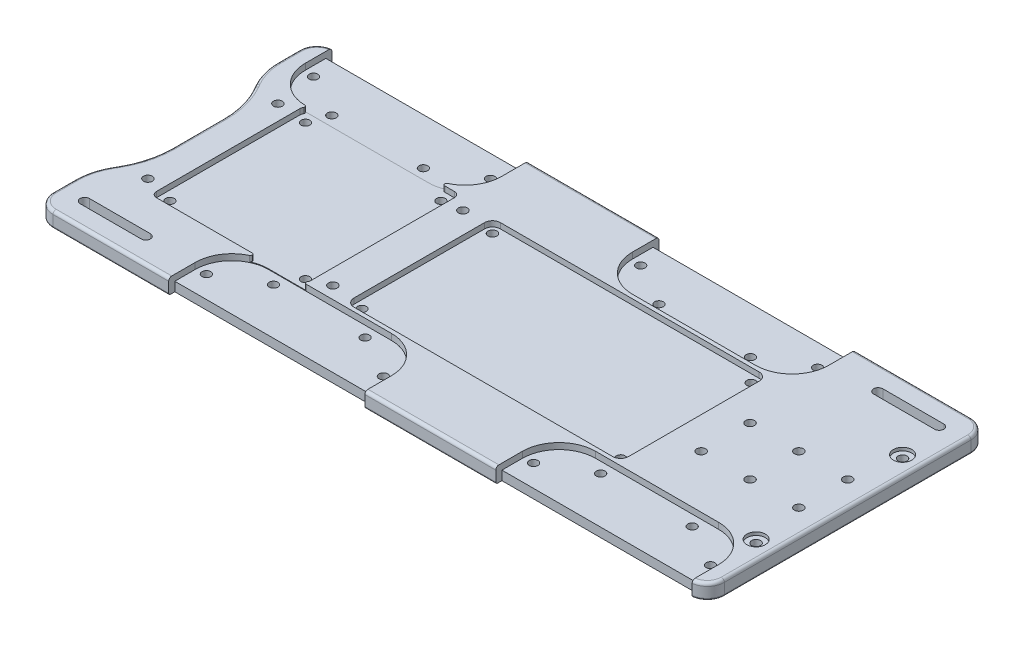
SolidWorks part; units mm, degrees
ref_plane "前视基准面" through (0, 0, 0) normal (0, 0, 1) x (1, 0, 0)
ref_plane "上视基准面" through (0, 0, 0) normal (0, 1, 0) x (1, 0, 0)
ref_plane "右视基准面" through (0, 0, 0) normal (1, 0, 0) x (0, 0, -1)
sketch "草图1" plane through (0, 0, 0) normal (0, 1, 0) x (1, 0, 0)
  line L1 (-105, -46) -> (105, -46)
  line L2 (-105, -46) -> (-105, 46)
  line L3 (-105, 46) -> (105, 46)
  line L4 (105, -46) -> (105, 46)
  line L5 (-105, -46) -> (105, 46) construction
  line L6 (-105, 46) -> (105, -46) construction
  point P0 (0, 0)
  dimension "D1" = 92
  dimension "D2" = 210
extrude "凸台-拉伸1" add sketch "草图1" along normal blind 5
sketch "草图7" plane through (0, 0, 0) normal (0, -1, 0) x (1, 0, 0)
  circle A0 centre (-101.85, -36.8) radius 1.425
  circle A1 centre (-87.85, -28.8) radius 1.425
  circle A2 centre (-57.85, -28.8) radius 1.425
  circle A3 centre (-43.85, -36.8) radius 1.425
  circle A4 centre (5.35, -36.8) radius 1.425
  circle A5 centre (19.35, -28.8) radius 1.425
  circle A6 centre (49.35, -28.8) radius 1.425
  circle A7 centre (63.35, -36.8) radius 1.425
  circle A8 centre (101.85, 36.8) radius 1.425
  circle A9 centre (87.85, 28.8) radius 1.425
  circle A10 centre (57.85, 28.8) radius 1.425
  circle A11 centre (43.85, 36.8) radius 1.425
  circle A12 centre (-5.35, 36.8) radius 1.425
  circle A13 centre (-19.35, 28.8) radius 1.425
  circle A14 centre (-49.35, 28.8) radius 1.425
  circle A15 centre (-63.35, 36.8) radius 1.425
  dimension "D1" = 2.85
  dimension "D2" = 2.85
  dimension "D3" = 2.85
  dimension "D4" = 2.85
  dimension "D5" = 2.85
  dimension "D6" = 2.85
  dimension "D7" = 2.85
  dimension "D8" = 2.85
  dimension "D9" = 2.85
  dimension "D10" = 2.85
  dimension "D11" = 2.85
  dimension "D12" = 2.85
  dimension "D13" = 2.85
  dimension "D14" = 2.85
  dimension "D15" = 2.85
  dimension "D16" = 2.85
extrude "切除-拉伸2" cut sketch "草图7" against normal blind 10
sketch "草图8" plane through (0, 5, 0) normal (0, 1, 0) x (1, 0, 0)
sketch "草图9" plane through (-105, 0, 0) normal (-1, 0, 0) x (0, 0, 1)
  line L1 (-46, 5) -> (46, 5)
  line L2 (-46, 5) -> (-46, 0)
  line L3 (-46, 0) -> (46, 0)
  line L12 (46, 5) -> (46, 0)
extrude "凸台-拉伸2" add sketch "草图9" along normal blind 5
sketch "草图10" plane through (105, 0, 0) normal (1, 0, 0) x (0, 0, -1)
  line L1 (-46, 5) -> (46, 5)
  line L2 (-46, 5) -> (-46, 0)
  line L3 (-46, 0) -> (46, 0)
  line L4 (46, 5) -> (46, 0)
extrude "凸台-拉伸3" add sketch "草图10" along normal blind 5
sketch "草图11" plane through (0, 5, 0) normal (0, 1, 0) x (1, 0, 0)
  line L0 (-110, 0) -> (-110, 28)
  line L2 (-110, 28) -> (-103, 15.8756)
  line L3 (-103, 15.8756) -> (-103, -15.8756)
  line L4 (-103, -15.8756) -> (-110, -28)
  line L5 (-110, -28) -> (-110, 0)
  dimension "D1" = 28
  dimension "D2" = 28
  dimension "D3" = 30
  dimension "D4" = 30
  dimension "D5" = 7
extrude "切除-拉伸4" cut sketch "草图11" against normal blind 5
fillet "圆角1" radius 20 2 edges at (-110, 2.5, 28) (-110, 2.5, -28)
fillet "圆角2" radius 28 2 edges at (-103, 2.5, 15.8756) (-103, 2.5, -15.8756)
fillet "圆角3" radius 5.6 4 edges at (110, 2.5, -46) (-110, 2.5, 46) (110, 2.5, 46) (-110, 2.5, -46)
sketch "草图13" plane through (0, 5, 0) normal (0, 1, 0) x (1, 0, 0)
  line L0 (-103, 0) -> (110, 0) construction
  line L1 (-103, -8.3731) -> (-103, 8.3731) construction
  line L4 (-93, 25.3) -> (-42.4, 25.3)
  line L5 (-93, 25.3) -> (-93, -25.3)
  line L6 (-93, -25.3) -> (-42.4, -25.3)
  line L7 (-42.4, 25.3) -> (-42.4, -25.3)
  line L8 (-93, 25.3) -> (-42.4, -25.3) construction
  line L9 (-93, -25.3) -> (-42.4, 25.3) construction
  point P6 (-67.7, 0)
  dimension "D1" = 50.6
  dimension "D2" = 50.6
  dimension "D3" = 10
extrude "切除-拉伸5" cut sketch "草图13" against normal blind 1.8
fillet "圆角4" radius 1.8 4 edges at (-42.4, 4.1, 25.3) (-93, 4.1, 25.3) (-42.4, 4.1, -25.3) (-93, 4.1, -25.3)
sketch "草图14" plane through (0, 3.2, 0) normal (0, 1, 0) x (1, 0, 0)
  line L0 (-44.2, 25.3) -> (-91.2, 25.3) construction
  line L1 (-93, 23.5) -> (-93, -23.5) construction
  line L2 (-93, 0) -> (-42.4, 0) construction
  line L3 (-93, 23.5) -> (-93, -23.5) construction
  line L4 (-42.4, -23.5) -> (-42.4, 23.5) construction
  line L6 (-67.7, 25.3) -> (-67.7, -25.3) construction
  line L7 (-91.2, -25.3) -> (-44.2, -25.3) construction
  circle A0 centre (-89.9, 22.2) radius 1.425
  circle A1 centre (-45.5, 22.2) radius 1.425
  circle A2 centre (-45.5, -22.2) radius 1.425
  circle A3 centre (-89.9, -22.2) radius 1.425
  dimension "D3" = 2.85
  dimension "D1" = 3.1
  dimension "D2" = 3.1
extrude "切除-拉伸6" cut sketch "草图14" against normal blind 3
sketch "草图15" plane through (0, 5, 0) normal (0, 1, 0) x (1, 0, 0)
  line L0 (-103, 0) -> (110, 0) construction
  line L1 (-103, -8.3731) -> (-103, 8.3731) construction
  line L2 (110, 40.4) -> (110, -40.4) construction
  line L3 (-42.4, -23.5) -> (-42.4, 23.5) construction
  line L4 (-30.4, 24) -> (59.6, 24)
  line L5 (-30.4, 24) -> (-30.4, -24)
  line L6 (-30.4, -24) -> (59.6, -24)
  line L7 (59.6, 24) -> (59.6, -24)
  line L8 (-30.4, 24) -> (59.6, -24) construction
  line L9 (-30.4, -24) -> (59.6, 24) construction
  line L10 (-42.4, -23.5) -> (-42.4, 23.5)
  point P6 (14.6, 0)
  dimension "D1" = 48
  dimension "D2" = 90
  dimension "D3" = 12
extrude "切除-拉伸7" cut sketch "草图15" against normal blind 1.8 contours L7 L4 L5 L6 region at (14.6, 5, 0)
fillet "圆角5" radius 2.6 4 edges at (59.6, 4.1, -24) (59.6, 4.1, 24) (-30.4, 4.1, 24) (-30.4, 4.1, -24)
sketch "草图16" plane through (0, 3.2, 0) normal (0, 1, 0) x (1, 0, 0)
  line L0 (-30.4, 0) -> (59.6, 0) construction
  line L1 (-30.4, 21.4) -> (-30.4, -21.4) construction
  line L2 (59.6, 21.4) -> (59.6, -21.4) construction
  line L3 (14.6, 24) -> (14.6, -24) construction
  line L4 (-27.8, 24) -> (57, 24) construction
  line L5 (-27.8, -24) -> (57, -24) construction
  circle A0 centre (-27.8, -21.4) radius 1.45
  circle A1 centre (-27.8, 21.4) radius 1.45
  circle A2 centre (57, -21.4) radius 1.45
  circle A3 centre (57, 21.4) radius 1.45
  dimension "D1" = 2.9
  dimension "D2" = 2.6
  dimension "D3" = 2.6
extrude "切除-拉伸8" cut sketch "草图16" against normal blind 3
sketch "草图18" plane through (0, 5, 0) normal (0, 1, 0) x (1, 0, 0)
  line L0 (59.6, 0) -> (110, 0) construction
  line L3 (59.6, 21.4) -> (59.6, -21.4) construction
  line L4 (110, 40.4) -> (110, -40.4) construction
  line L5 (102, 38) -> (82, 38) construction
  line L9 (102, 36.5) -> (82, 36.5)
  line L10 (102, 39.5) -> (82, 39.5)
  line L12 (104.4, 46) -> (-104.4, 46) construction
  line L13 (0, 46) -> (0, -46) construction
  line L16 (-104.4, -46) -> (104.4, -46) construction
  line L20 (-102, -38) -> (-82, -38) construction
  line L21 (-102, -36.5) -> (-82, -36.5)
  line L22 (-102, -39.5) -> (-82, -39.5)
  circle A0 centre (102, 8) radius 1.45
  circle A2 centre (86, 8) radius 1.45
  circle A3 centre (70, 8) radius 1.45
  circle A4 centre (102, -8) radius 1.45
  circle A5 centre (86, -8) radius 1.45
  circle A6 centre (70, -8) radius 1.45
  circle A9 centre (104, 24) radius 1.45
  arc A10 (102, 36.5) -> (102, 39.5) centre (102, 38) ccw
  arc A11 (82, 39.5) -> (82, 36.5) centre (82, 38) ccw
  circle A12 centre (104, -24) radius 1.45
  arc A17 (-102, -36.5) -> (-102, -39.5) centre (-102, -38) ccw
  arc A18 (-82, -39.5) -> (-82, -36.5) centre (-82, -38) ccw
  point P20 (92, 38)
  point P37 (92, -38)
  point P44 (-92, -38)
  dimension "D2" = 2.9
  dimension "D4" = 2.9
  dimension "D5" = 2.9
  dimension "D8" = 1.5
  dimension "D12" = 2.9
  dimension "D1" = 8
  dimension "D3" = 8
  dimension "D6" = 16
  dimension "D7" = 16
  dimension "D9" = 20
  dimension "D10" = 8
  dimension "D11" = 8
  dimension "D13" = 6
  dimension "D14" = 24
extrude "切除-拉伸9" cut sketch "草图18" against normal through all
sketch "草图19" plane through (0, 5, 0) normal (0, 1, 0) x (1, 0, 0)
  circle A0 centre (104, 24) radius 3.025
  circle A1 centre (104, -24) radius 3.025
  dimension "D1" = 6.05
  dimension "D2" = 6.05
extrude "切除-拉伸10" cut sketch "草图19" against normal blind 1.04
fillet "圆角6" radius 0.6 16 edges at (-108.3598, 0, 44.3598) (-110, 0, 36.8795) (-109.3185, 0, 28.1826) (-107.0359, 0, 22.866) (-103.9541, 0, 15.62) (-103, 0, 0) (-103.9541, 0, -15.62) (-107.0359, 0, -22.866) (-109.3185, 0, -28.1826) (-110, 0, -36.8795) (-108.3598, 0, -44.3598) (0, 0, -46) (108.3598, 0, -44.3598) (110, 0, 0) (108.3598, 0, 44.3598) (0, 0, 46)
sketch "草图21" plane through (0, 0, 0) normal (0, -1, 0) x (1, 0, 0)
  line L0 (40.7, 46) -> (40.7, 37.3)
  line L1 (52.7, 25.3) -> (93, 25.3)
  line L2 (105, 37.3) -> (105, 46)
  line L3 (105, 46) -> (40.7, 46)
  line L4 (-66.5, 46) -> (-66.5, 37.3)
  line L5 (-54.5, 25.3) -> (-14.2, 25.3)
  line L6 (-2.2, 37.3) -> (-2.2, 46)
  line L7 (-2.2, 46) -> (-66.5, 46)
  line L8 (-105, -37.3) -> (-105, -46)
  line L9 (-105, -46) -> (-40.7, -46)
  line L10 (-93, -25.3) -> (-52.7, -25.3)
  line L11 (-40.7, -37.3) -> (-40.7, -46)
  line L12 (66.5, -46) -> (66.5, -37.3)
  line L13 (54.5, -25.3) -> (14.2, -25.3)
  line L14 (2.2, -37.3) -> (2.2, -46)
  line L15 (104.4, -46) -> (-104.4, -46) construction
  line L16 (2.2, -46) -> (66.5, -46)
  line L18 (-66.5, 46) -> (-2.2, 46)
  line L19 (-66.5, 46) -> (-66.5, 44)
  line L20 (-66.5, 44) -> (-2.2, 44)
  line L21 (-2.2, 46) -> (-2.2, 44)
  line L22 (105, 46) -> (40.7, 46)
  line L23 (105, 46) -> (105, 44)
  line L24 (105, 44) -> (40.7, 44)
  line L25 (40.7, 46) -> (40.7, 44)
  line L26 (66.5, -46) -> (2.2, -46)
  line L27 (66.5, -46) -> (66.5, -44)
  line L28 (66.5, -44) -> (2.2, -44)
  line L29 (2.2, -46) -> (2.2, -44)
  line L30 (-105, -46) -> (-40.7, -46)
  line L31 (-105, -46) -> (-105, -44)
  line L32 (-105, -44) -> (-40.7, -44)
  line L33 (-40.7, -46) -> (-40.7, -44)
  arc A0 (40.7, 37.3) -> (52.7, 25.3) centre (52.7, 37.3) ccw
  arc A1 (93, 25.3) -> (105, 37.3) centre (93, 37.3) ccw
  arc A2 (-66.5, 37.3) -> (-54.5, 25.3) centre (-54.5, 37.3) ccw
  arc A3 (-14.2, 25.3) -> (-2.2, 37.3) centre (-14.2, 37.3) ccw
  arc A4 (-105, -37.3) -> (-93, -25.3) centre (-93, -37.3) cw
  arc A5 (-52.7, -25.3) -> (-40.7, -37.3) centre (-52.7, -37.3) cw
  arc A6 (66.5, -37.3) -> (54.5, -25.3) centre (54.5, -37.3) ccw
  arc A7 (14.2, -25.3) -> (2.2, -37.3) centre (14.2, -37.3) ccw
  dimension "D1" = 2
  dimension "D2" = 2
  dimension "D3" = 2
  dimension "D4" = 2
sketch "草图22" plane through (0, 5, 0) normal (0, 1, 0) x (1, 0, 0)
  line L0 (-105, 46) -> (-40.7, 46) construction
  line L1 (-40.7, 37.3) -> (-40.7, 46) construction
  line L2 (-93, 25.3) -> (-52.7, 25.3) construction
  line L3 (-105, 37.3) -> (-105, 46) construction
  line L4 (2.2, 46) -> (66.5, 46) construction
  line L5 (66.5, 46) -> (66.5, 37.3) construction
  line L6 (54.5, 25.3) -> (14.2, 25.3) construction
  line L7 (2.2, 37.3) -> (2.2, 46) construction
  line L8 (105, -46) -> (40.7, -46) construction
  line L9 (40.7, -46) -> (40.7, -37.3) construction
  line L10 (52.7, -25.3) -> (93, -25.3) construction
  line L11 (105, -37.3) -> (105, -46) construction
  line L12 (-66.5, -46) -> (-66.5, -37.3) construction
  line L13 (-2.2, -46) -> (-66.5, -46) construction
  line L14 (-2.2, -37.3) -> (-2.2, -46) construction
  line L15 (-54.5, -25.3) -> (-14.2, -25.3) construction
  line L16 (-105, 46) -> (-40.7, 46)
  line L17 (-40.7, 37.3) -> (-40.7, 46)
  line L18 (-93, 25.3) -> (-52.7, 25.3)
  line L19 (-105, 37.3) -> (-105, 46)
  line L20 (2.2, 46) -> (66.5, 46)
  line L21 (66.5, 46) -> (66.5, 37.3)
  line L22 (54.5, 25.3) -> (14.2, 25.3)
  line L23 (2.2, 37.3) -> (2.2, 46)
  line L24 (105, -46) -> (40.7, -46)
  line L25 (40.7, -46) -> (40.7, -37.3)
  line L26 (52.7, -25.3) -> (93, -25.3)
  line L27 (105, -37.3) -> (105, -46)
  line L28 (-66.5, -46) -> (-66.5, -37.3)
  line L29 (-2.2, -46) -> (-66.5, -46)
  line L30 (-2.2, -37.3) -> (-2.2, -46)
  line L31 (-54.5, -25.3) -> (-14.2, -25.3)
  arc A0 (-52.7, 25.3) -> (-40.7, 37.3) centre (-52.7, 37.3) ccw construction
  arc A1 (-105, 37.3) -> (-93, 25.3) centre (-93, 37.3) ccw construction
  arc A2 (54.5, 25.3) -> (66.5, 37.3) centre (54.5, 37.3) ccw construction
  arc A3 (2.2, 37.3) -> (14.2, 25.3) centre (14.2, 37.3) ccw construction
  arc A4 (52.7, -25.3) -> (40.7, -37.3) centre (52.7, -37.3) ccw construction
  arc A5 (105, -37.3) -> (93, -25.3) centre (93, -37.3) ccw construction
  arc A6 (-54.5, -25.3) -> (-66.5, -37.3) centre (-54.5, -37.3) ccw construction
  arc A7 (-2.2, -37.3) -> (-14.2, -25.3) centre (-14.2, -37.3) ccw construction
  arc A8 (-52.7, 25.3) -> (-40.7, 37.3) centre (-52.7, 37.3) ccw
  arc A9 (-105, 37.3) -> (-93, 25.3) centre (-93, 37.3) ccw
  arc A10 (54.5, 25.3) -> (66.5, 37.3) centre (54.5, 37.3) ccw
  arc A11 (2.2, 37.3) -> (14.2, 25.3) centre (14.2, 37.3) ccw
  arc A12 (52.7, -25.3) -> (40.7, -37.3) centre (52.7, -37.3) ccw
  arc A13 (105, -37.3) -> (93, -25.3) centre (93, -37.3) ccw
  arc A14 (-54.5, -25.3) -> (-66.5, -37.3) centre (-54.5, -37.3) ccw
  arc A15 (-2.2, -37.3) -> (-14.2, -25.3) centre (-14.2, -37.3) ccw
extrude "切除-拉伸11" cut sketch "草图22" against normal blind 2
fillet "圆角7" radius 0.6 4 edges at (-91.2, 4.1, -25.3) (-52.7, 4.1, -25.3) (-44.2, 4.1, 25.3) (-54.5, 4.1, 25.3)
extrude "切除-拉伸14" cut sketch "草图21" against normal through all contours L4 L20 L6 L7 | L24 L2 L3 L0 | L12 L28 L14 L16 | L32 L8 L9 L11 | L31 L30 L33 L32 | L27 L26 L29 L28 | L23 L22 L25 L24 | L19 L18 L21 L20 region at (72.85, 0, 45) region at (-34.35, 0, 45) region at (-72.85, 0, -45) region at (34.35, 0, -45)
sketch "草图23" plane through (0, 5, 0) normal (0, 1, 0) x (1, 0, 0)
  line L0 (-103, -8.3731) -> (-103, 8.3731) construction
  line L1 (-91.2, -25.3) -> (-59.8666, -25.3) construction
  line L2 (-44.2, 25.3) -> (-47.3334, 25.3) construction
  line L3 (-42.4, -23.5) -> (-42.4, 23.5) construction
  line L4 (-42.4, -23.5) -> (-42.4, 23.5) construction
  circle A0 centre (-37.4, 21.3) radius 1.45
  circle A1 centre (-37.4, -21.3) radius 1.45
  circle A2 centre (-98, -21.3) radius 1.45
  circle A3 centre (-98, 21.3) radius 1.45
  dimension "D9" = 2.9
  dimension "D10" = 2.9
  dimension "D11" = 2.9
  dimension "D12" = 2.9
  dimension "D1" = 5
  dimension "D2" = 5
  dimension "D3" = 4
  dimension "D4" = 4
  dimension "D5" = 5
  dimension "D6" = 5
  dimension "D7" = 4
  dimension "D8" = 4
extrude "切除-拉伸15" cut sketch "草图23" against normal blind 10
fillet "圆角8" radius 1 18 edges at (85.45, 5, -46) (108.3598, 5, -44.3598) (108.5665, 5, 44.1417) (-108.5665, 5, -44.1417) (-110, 5, -36.8795) (-109.3185, 5, -28.1826) (-107.0359, 5, -22.866) (-103.9541, 5, -15.62) (-103, 5, 0) (-103.9541, 5, 15.62) (-107.0359, 5, 22.866) (-109.3185, 5, 28.1826) (-110, 5, 36.8795) (-19.25, 5, -46) (110, 5, 0) (19.25, 5, 46) (-108.3598, 5, 44.3598) (-85.45, 5, 46)
